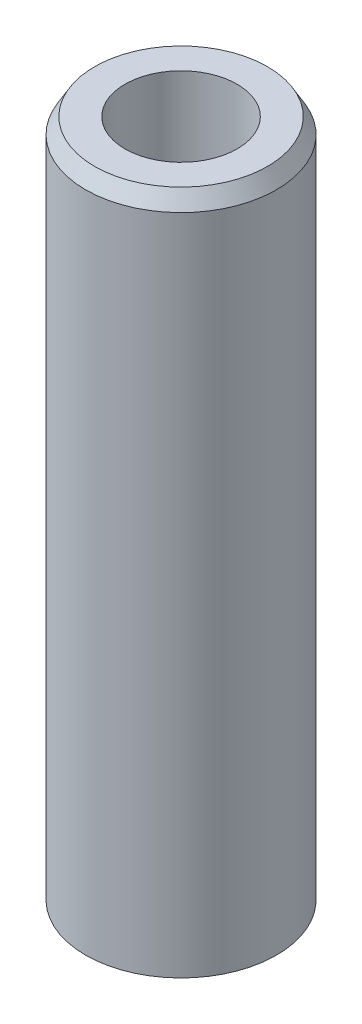
SolidWorks part; units mm, degrees
ref_plane "Front Plane" through (0, 0, 0) normal (0, 0, 1) x (1, 0, 0)
ref_plane "Top Plane" through (0, 0, 0) normal (0, 1, 0) x (1, 0, 0)
ref_plane "Right Plane" through (0, 0, 0) normal (1, 0, 0) x (0, 0, -1)
sketch "Sketch1" plane through (0, 0, 0) normal (0, 1, 0) x (1, 0, 0)
  circle A0 centre (0, 0) radius 20
  dimension "SHAFT_OD" = 40
extrude "Boss-Extrude1" add sketch "Sketch1" along normal blind 144.0078
sketch "Sketch2" plane through (0, 0, 0) normal (0, 1, 0) x (1, 0, 0)
  circle A0 centre (0, 0) radius 11.7461
  dimension "BORE_D" = 23.4922
extrude "Cut-Extrude1" cut sketch "Sketch2" along normal through all
chamfer "Chamfer1" distance 3.2848 angle 30 2 edges at (0, 144.0078, 20) (0, 0, 20) first distance on face at (0, 144.0078, 20) first distance on face at (0, 0, 11.7461)
